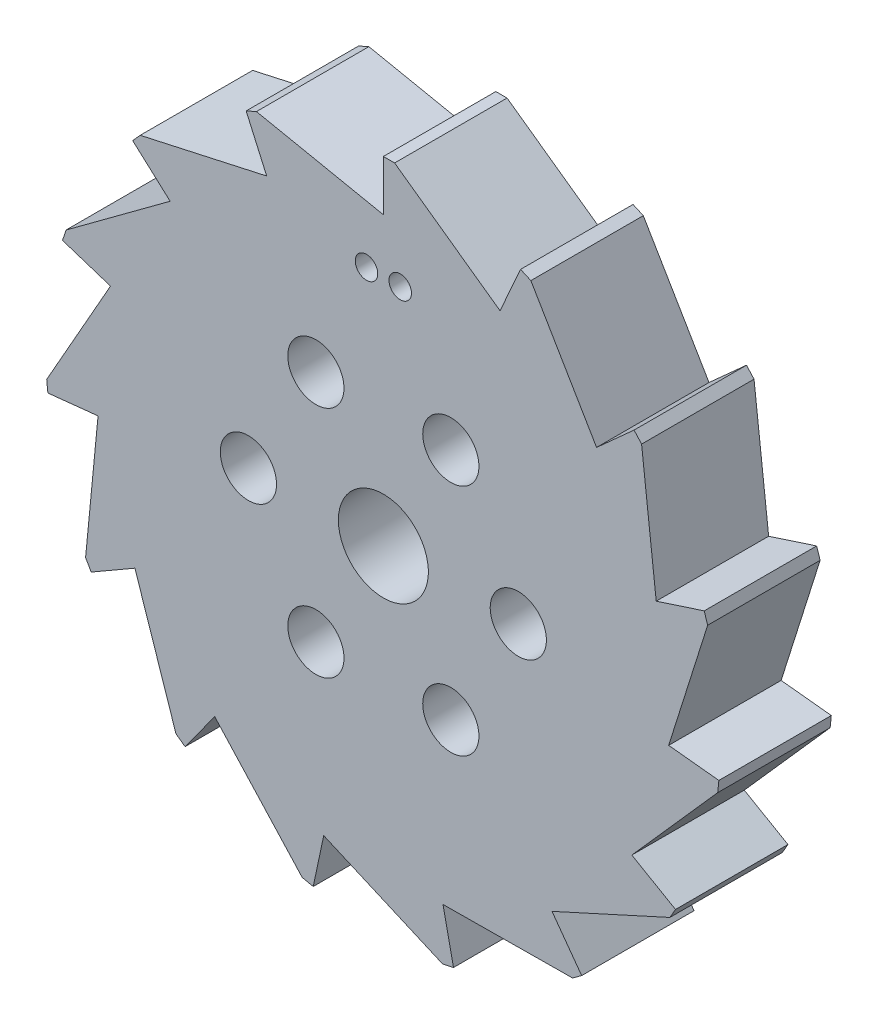
SolidWorks part; units mm, degrees
ref_plane "Front Plane" through (0, 0, 0) normal (0, 0, 1) x (1, 0, 0)
ref_plane "Top Plane" through (0, 0, 0) normal (0, 1, 0) x (1, 0, 0)
ref_plane "Right Plane" through (0, 0, 0) normal (1, 0, 0) x (0, 0, -1)
sketch "Sketch1" plane through (0, 0, 0) normal (0, 0, 1) x (1, 0, 0)
  line L0 (0, 25.5126) -> (0, 30)
  line L1 (0, 30) -> (1.0009, 30)
  line L2 (1.0009, 30) -> (10.3769, 23.307)
  line L3 (13.1165, 26.9993) -> (18.9596, 17.0713)
  line L4 (10.3769, 23.307) -> (12.2021, 27.4064)
  line L5 (12.2021, 27.4064) -> (13.1165, 26.9993)
  line L6 (22.9641, 19.3301) -> (24.264, 7.8838)
  line L7 (18.9596, 17.0713) -> (22.2943, 20.0739)
  line L8 (22.2943, 20.0739) -> (22.9641, 19.3301)
  line L9 (28.841, 8.3186) -> (25.3729, -2.6668)
  line L10 (24.264, 7.8838) -> (28.5317, 9.2705)
  line L11 (28.5317, 9.2705) -> (28.841, 8.3186)
  line L12 (29.731, -4.1313) -> (22.0946, -12.7563)
  line L13 (25.3729, -2.6668) -> (29.8357, -3.1359)
  line L14 (29.8357, -3.1359) -> (29.731, -4.1313)
  line L15 (25.4803, -15.8668) -> (14.996, -20.6402)
  line L16 (22.0946, -12.7563) -> (25.9808, -15)
  line L17 (25.9808, -15) -> (25.4803, -15.8668)
  line L18 (16.8238, -24.8588) -> (5.3044, -24.9551)
  line L19 (14.996, -20.6402) -> (17.6336, -24.2705)
  line L20 (17.6336, -24.2705) -> (16.8238, -24.8588)
  line L21 (5.2583, -29.5525) -> (-5.3044, -24.9551)
  line L22 (5.3044, -24.9551) -> (6.2374, -29.3444)
  line L23 (6.2374, -29.3444) -> (5.2583, -29.5525)
  line L24 (-7.2164, -29.1363) -> (-14.996, -20.6402)
  line L25 (-5.3044, -24.9551) -> (-6.2374, -29.3444)
  line L26 (-6.2374, -29.3444) -> (-7.2164, -29.1363)
  line L27 (-18.4433, -23.6822) -> (-22.0946, -12.7563)
  line L28 (-14.996, -20.6402) -> (-17.6336, -24.2705)
  line L29 (-17.6336, -24.2705) -> (-18.4433, -23.6822)
  line L30 (-26.4812, -14.1332) -> (-25.3729, -2.6668)
  line L31 (-22.0946, -12.7563) -> (-25.9808, -15)
  line L32 (-25.9808, -15) -> (-26.4812, -14.1332)
  line L33 (-29.9403, -2.1404) -> (-24.264, 7.8838)
  line L34 (-25.3729, -2.6668) -> (-29.8357, -3.1359)
  line L35 (-29.8357, -3.1359) -> (-29.9403, -2.1404)
  line L36 (-28.2224, 10.2224) -> (-18.9596, 17.0713)
  line L37 (-24.264, 7.8838) -> (-28.5317, 9.2705)
  line L38 (-28.5317, 9.2705) -> (-28.2224, 10.2224)
  line L39 (-21.6246, 20.8177) -> (-10.3769, 23.307)
  line L40 (-18.9596, 17.0713) -> (-22.2943, 20.0739)
  line L41 (-22.2943, 20.0739) -> (-21.6246, 20.8177)
  line L42 (-11.2877, 27.8135) -> (0, 25.5126)
  line L43 (-10.3769, 23.307) -> (-12.2021, 27.4064)
  line L44 (-12.2021, 27.4064) -> (-11.2877, 27.8135)
  line L45 (0, 0) -> (14.3091, 20.5) construction
  circle A0 centre (0, 0) radius 25 construction
  circle A1 centre (0, 0) radius 4
  dimension "D1" = 50
  dimension "D8" = 8
  dimension "D2" = 4.4874
  dimension "D3" = 1.0009
  dimension "D4" = 25.5126
  dimension "D6" = 25
  dimension "D7" = 10.3769
  dimension "D5" = 15
extrude "Boss-Extrude2" add sketch "Sketch1" along normal blind 10 contours L9 L13 L14 L12 L16 L17 L15 L19 L20 L18 L22 L23 L21 L25 L26 L24 L28 L29 L27 L31 L32 L30 L34 L35 L33 L37 L38 L36 L40 L41 L39 L43 L44 L42 L0 L1 L2 L4 L5 L3 L7 L8 L6 L10 L11
sketch "Sketch2" plane through (0, 0, 0) normal (0, 0, -1) x (-1, 0, 0)
  line L0 (0, 0) -> (0, 24.573) construction
  line L1 (-1.5, 20.7144) -> (0, 20.7144) construction
  line L2 (0, 20.7144) -> (1.5, 20.7144) construction
  circle A0 centre (0, 0) radius 4
  circle A2 centre (-12, 0) radius 2.5
  circle A3 centre (-6, 10.3923) radius 2.5
  circle A4 centre (6, 10.3923) radius 2.5
  circle A5 centre (12, 0) radius 2.5
  circle A6 centre (6, -10.3923) radius 2.5
  circle A7 centre (-6, -10.3923) radius 2.5
  circle A8 centre (1.5, 20.7144) radius 1
  circle A9 centre (-1.5, 20.7144) radius 1
  point P18 (0, 0)
  dimension "D1" = 8
  dimension "D3" = 12
  dimension "D2" = 5
  dimension "D5" = 2
  dimension "D6" = 1.5
  dimension "D4" = 6
extrude "Cut-Extrude1" cut sketch "Sketch2" against normal blind 10
